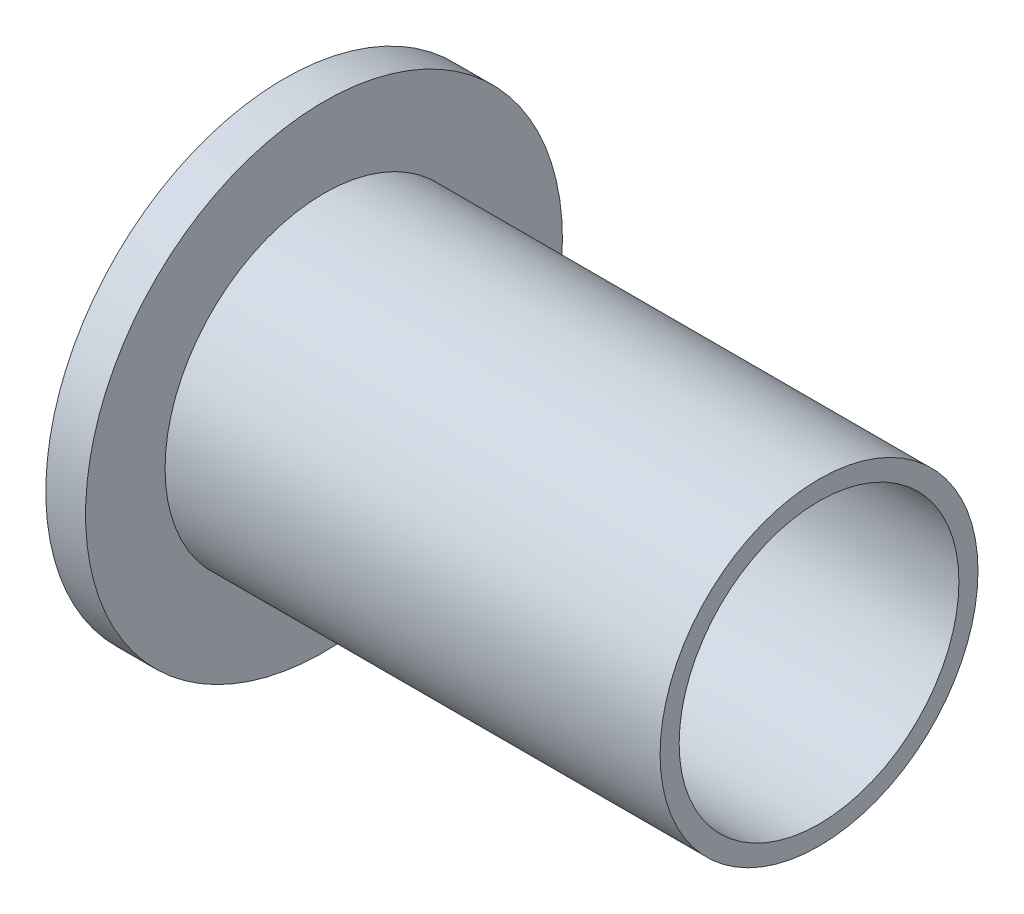
SolidWorks part; units mm, degrees
ref_plane "Front Plane" through (0, 0, 0) normal (0, 0, 1) x (1, 0, 0)
ref_plane "Top Plane" through (0, 0, 0) normal (0, 1, 0) x (1, 0, 0)
ref_plane "Right Plane" through (0, 0, 0) normal (1, 0, 0) x (0, 0, -1)
sketch "Sketch1" plane through (0, 0, 0) normal (0, 0, 1) x (1, 0, 0)
  line L0 (0, 0) -> (0, 9.525)
  line L1 (0, 9.525) -> (1.5875, 9.525)
  line L2 (1.5875, 9.525) -> (1.5875, 6.35)
  line L3 (1.5875, 6.35) -> (21.3639, 6.35)
  line L4 (21.3639, 6.35) -> (21.3639, 0)
  line L5 (21.3639, 0) -> (0, 0)
  line L6 (21.3639, 0) -> (21.3639, 5.588)
  line L7 (21.3639, 5.588) -> (0, 5.588)
  dimension "D1" = 9.525
  dimension "D2" = 6.35
  dimension "D3" = 5.588
  dimension "D4" = 19.7764
  dimension "D5" = 1.5875
revolve "Revolve1" add sketch "Sketch1" angle 360 about L5 region at (0.2172, 7.5565, 0)
